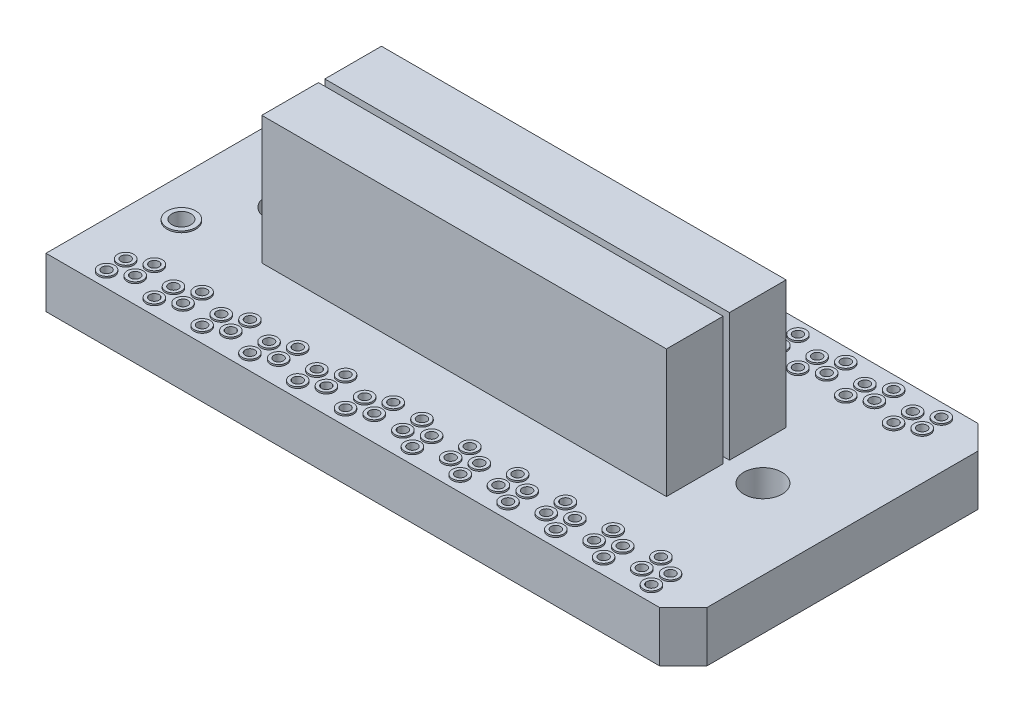
SolidWorks part; units mm, degrees
ref_plane "Front Plane" through (0, 0, 0) normal (0, 0, 1) x (1, 0, 0)
ref_plane "Top Plane" through (0, 0, 0) normal (0, 1, 0) x (1, 0, 0)
ref_plane "Right Plane" through (0, 0, 0) normal (1, 0, 0) x (0, 0, -1)
sketch "Sketch1" plane through (0, 0, 0) normal (0, 1, 0) x (1, 0, 0)
  line L0 (-10, -5) -> (10, -5)
  line L1 (-10, -5) -> (-10, 5)
  line L2 (10, -5) -> (10, 5)
  line L3 (-10, 5) -> (10, 5)
  line L4 (-10, -5) -> (10, 5) construction
  line L5 (10, -5) -> (-10, 5) construction
  point P1 (0, 0)
  dimension "D1" = 20
  dimension "D2" = 10
extrude "PCB" add sketch "Sketch1" along normal blind 1.5875
sketch "Sketch2" plane through (0, 1.5875, 0) normal (0, 1, 0) x (1, 0, 0)
  line L1 (-6.35, -0.1) -> (6.35, -0.1)
  line L2 (-6.35, -0.1) -> (-6.35, -1.878)
  line L3 (-6.35, -1.878) -> (6.35, -1.878)
  line L4 (6.35, -0.1) -> (6.35, -1.878)
  line L10 (0, 0) -> (0, 5.3763) construction
  line L12 (6.35, -0.1) -> (-6.35, -1.878) construction
  point P4 (0, 0)
  point P8 (0, -0.989)
  dimension "D1" = 12.7
  dimension "D2" = 1.778
  dimension "D4" = 0.1
extrude "Connector" add sketch "Sketch2" along normal blind 4.0132
mirror "Mirror1" about plane through (0, 0, 0) normal (0, 0, 1) of "Connector"
sketch "Sketch3" plane through (0, 1.5875, 0) normal (0, 1, 0) x (1, 0, 0)
  line L0 (0, 0) -> (0, -6.2242) construction
  line L1 (-0.45, -3.65) -> (-0.45, -4.25) construction
  line L2 (-1.05, -3.95) -> (-1.05, -4.55) construction
  line L3 (-1.05, -3.95) -> (-0.45, -3.95) construction
  line L4 (-10, -5) -> (10, -5) construction
  circle A0 centre (-0.45, -3.65) radius 0.15
  circle A1 centre (-0.45, -4.25) radius 0.15
  circle A2 centre (-1.05, -3.95) radius 0.15
  circle A3 centre (-1.05, -4.55) radius 0.15
  point P10 (0, 0)
  dimension "D1" = 0.6
  dimension "D2" = 0.3
  dimension "D3" = 0.3
  dimension "D6" = 0.3
  dimension "D7" = 0.3
  dimension "D4" = 0.6
  dimension "D5" = 0.6
  dimension "D8" = 0.45
  dimension "D9" = 0.45
extrude "Cut-Extrude1" cut sketch "Sketch3" against normal through all
sketch "Sketch4" plane through (0, 1.5875, 0) normal (0, 1, 0) x (1, 0, 0)
  circle A0 centre (-0.45, -3.65) radius 0.15 construction
  circle A1 centre (-0.45, -4.25) radius 0.15 construction
  circle A2 centre (-1.05, -4.55) radius 0.15 construction
  circle A3 centre (-1.05, -3.95) radius 0.15 construction
  circle A4 centre (-0.45, -3.65) radius 0.15
  circle A5 centre (-0.45, -4.25) radius 0.15
  circle A6 centre (-1.05, -4.55) radius 0.15
  circle A7 centre (-1.05, -3.95) radius 0.15
  circle A8 centre (-1.05, -4.55) radius 0.25
  circle A9 centre (-0.45, -4.25) radius 0.25
  circle A10 centre (-0.45, -3.65) radius 0.25
  circle A11 centre (-1.05, -3.95) radius 0.25
  dimension "D1" = 0.1
extrude "Boss-Extrude3" add sketch "Sketch4" along normal blind 0.05
sketch "Sketch5" plane through (0, 1.5875, 0) normal (0, 1, 0) x (1, 0, 0)
  line L0 (-10, 5) -> (-10, -5) construction
  line L1 (-10, -5) -> (10, -5) construction
  circle A0 centre (-8.75, -2) radius 0.3
  dimension "D1" = 0.6
  dimension "D2" = 1.25
  dimension "D3" = 3
extrude "Cut-Extrude2" cut sketch "Sketch5" against normal through all
sketch "Sketch6" plane through (0, 1.5875, 0) normal (0, 1, 0) x (1, 0, 0)
  circle A0 centre (-8.75, -2) radius 0.3 construction
  circle A1 centre (-8.75, -2) radius 0.3
  circle A2 centre (-8.75, -2) radius 0.45
  dimension "D1" = 0.15
extrude "Boss-Extrude4" add sketch "Sketch6" along normal blind 0.05
pattern_linear "LPattern1" count 6 spacing 1.5 along (-1, 0, 0) of "Boss-Extrude3", "Cut-Extrude1"
mirror "Mirror2" about plane through (0, 0, 0) normal (1, 0, 0) of "LPattern1"
mirror "Mirror3" about plane through (0, 0, 0) normal (0, 0, 1) of "Boss-Extrude4", "Cut-Extrude2", "Mirror2", "LPattern1"
chamfer "Chamfer1" distance 0.75 angle 45 2 edges at (10, 0.7937, -5) (10, 0.7937, 5)
sketch "Sketch8" plane through (0, 0, -1.878) normal (0, 0, 1) x (1, 0, 0)
  line L0 (-6.35, 2.5875) -> (6.35, 2.5875) construction
  line L3 (-6.35, 1.5875) -> (6.35, 1.5875) construction
  text T0 "OMNETICS" font "Arial" height 1.5
  dimension "D1" = 1
extrude "Boss-Extrude5" add sketch "Sketch8" against normal blind 0.01
sketch "Sketch9" plane through (0, 0, 0) normal (0, -1, 0) x (-1, 0, 0)
  circle A0 centre (-7.5, 0) radius 0.6
  circle A1 centre (7.5, 0) radius 0.6
  dimension "D3" = 1.2
  dimension "D4" = 1.2
  dimension "D1" = 7.5
  dimension "D2" = 7.5
extrude "Cut-Extrude3" cut sketch "Sketch9" against normal blind 10
